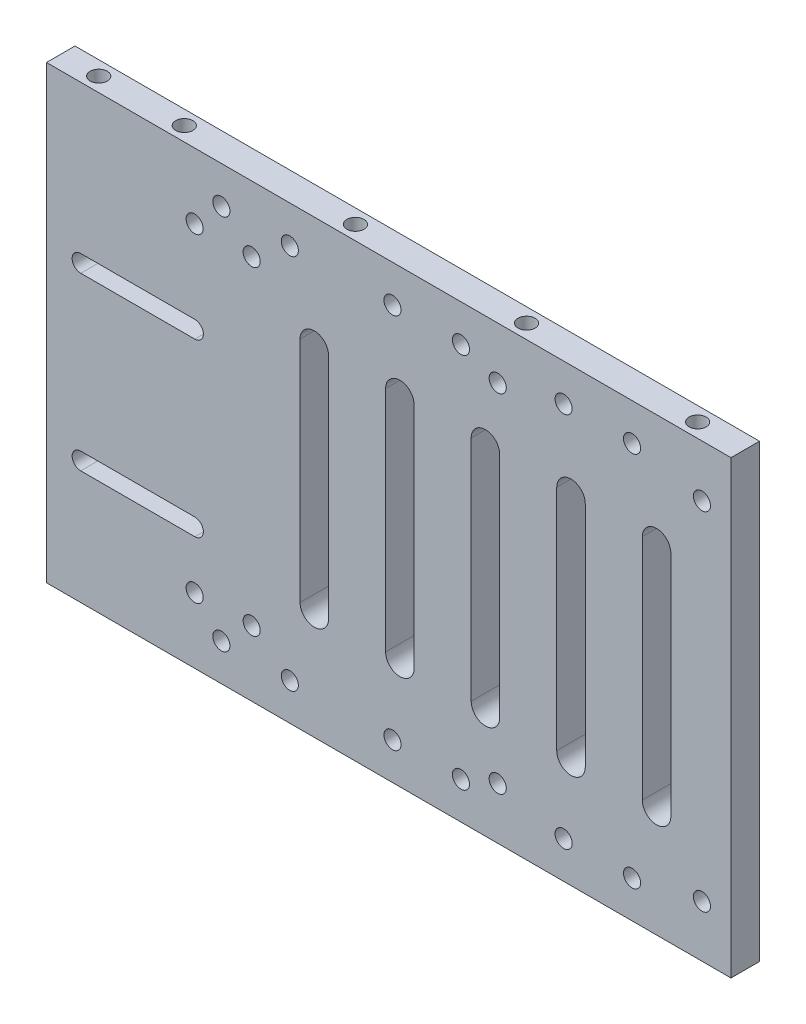
SolidWorks part; units mm, degrees
ref_plane "前视基准面" through (0, 0, 0) normal (0, 0, 1) x (1, 0, 0)
ref_plane "上视基准面" through (0, 0, 0) normal (0, 1, 0) x (1, 0, 0)
ref_plane "右视基准面" through (0, 0, 0) normal (1, 0, 0) x (0, 0, -1)
other "Configuration Table"
sketch "草图1" plane through (0, 0, 0) normal (0, 0, 1) x (1, 0, 0)
  line L1 (-60, -39.5) -> (60, -39.5)
  line L2 (-60, -39.5) -> (-60, 39.5)
  line L3 (-60, 39.5) -> (60, 39.5)
  line L4 (60, -39.5) -> (60, 39.5)
  line L5 (-60, -39.5) -> (60, 39.5) construction
  line L6 (-60, 39.5) -> (60, -39.5) construction
  point P0 (0, 0)
  dimension "D1" = 79
  dimension "D2" = 120
extrude "凸台-拉伸1" add sketch "草图1" along normal blind 5
sketch "草图2" plane through (0, 0, 0) normal (0, 0, -1) x (-1, 0, 0)
  circle A0 centre (-42.656, -33) radius 3.1
  circle A1 centre (-30.656, -33) radius 3.1
extrude "切除-拉伸1" cut sketch "草图2" against normal blind 1.5
sketch "草图3" plane through (0, 0, 1.5) normal (0, 0, -1) x (-1, 0, 0)
  circle A0 centre (-42.656, -33) radius 1.5
  circle A1 centre (-30.656, -33) radius 1.5
extrude "切除-拉伸2" cut sketch "草图3" against normal through all
pattern_linear "阵列(线性)1" count 3 spacing 30 along (-1, 0, 0) of "切除-拉伸1", "切除-拉伸2"
mirror "镜向2" about plane through (0, 0, 0) normal (0, 1, 0) of "阵列(线性)1"
sketch "草图4" plane through (0, 0, 0) normal (0, 0, -1) x (-1, 0, 0)
  line L0 (34, 12) -> (54, 12) construction
  line L1 (34, 15.1) -> (54, 15.1)
  line L2 (34, 8.9) -> (54, 8.9)
  line L3 (60, 39.5) -> (60, -39.5) construction
  line L4 (34.3421, -3) -> (54.815, -3) construction
  line L5 (34.3421, 17) -> (34.3421, -23) construction
  line L6 (54.815, 17) -> (54.815, -6) construction
  line L7 (34, -18) -> (54, -18) construction
  line L8 (34, -21.1) -> (54, -21.1)
  line L9 (34, -14.9) -> (54, -14.9)
  arc A4 (34, 15.1) -> (34, 8.9) centre (34, 12) ccw
  arc A5 (54, 8.9) -> (54, 15.1) centre (54, 12) ccw
  arc A6 (34, -21.1) -> (34, -14.9) centre (34, -18) cw
  arc A7 (54, -14.9) -> (54, -21.1) centre (54, -18) cw
  point P8 (44, 12)
  point P17 (44, -18)
  dimension "D1" = 20
  dimension "D2" = 6
extrude "切除-拉伸3" cut sketch "草图4" against normal blind 1.5
sketch "草图5" plane through (0, 0, 1.5) normal (0, 0, -1) x (-1, 0, 0)
  line L0 (54, 12) -> (34, 12) construction
  line L1 (54, 10.5) -> (34, 10.5)
  line L2 (54, 13.5) -> (34, 13.5)
  line L3 (60, 39.5) -> (60, -39.5) construction
  line L4 (34.3421, -3) -> (54.815, -3) construction
  line L5 (54.815, 17) -> (54.815, -6) construction
  line L6 (54, -18) -> (34, -18) construction
  line L7 (54, -16.5) -> (34, -16.5)
  line L8 (54, -19.5) -> (34, -19.5)
  arc A0 (54, 10.5) -> (54, 13.5) centre (54, 12) ccw
  arc A1 (34, 13.5) -> (34, 10.5) centre (34, 12) ccw
  arc A2 (54, -16.5) -> (54, -19.5) centre (54, -18) cw
  arc A3 (34, -19.5) -> (34, -16.5) centre (34, -18) cw
  point P4 (44, 12)
  point P18 (44, -18)
  dimension "D1" = 20
  dimension "D2" = 6
extrude "切除-拉伸4" cut sketch "草图5" against normal through all
sketch "草图7" plane through (0, -39.5, 0) normal (0, -1, 0) x (1, 0, 0)
  line L0 (46.656, 31) -> (46.656, 5) construction
  circle A0 centre (51.656, 2.5) radius 1.5
  circle A1 centre (21.656, 2.5) radius 1.5
  circle A2 centre (-8.344, 2.5) radius 1.5
  circle A3 centre (-38.344, 2.5) radius 1.5
  circle A4 centre (-53.344, 2.5) radius 1.5
  dimension "D1" = 5
  dimension "D2" = 15
extrude "切除-拉伸6" cut sketch "草图7" against normal blind 5
mirror "镜向3" about plane through (0, 0, 0) normal (0, 1, 0) of "切除-拉伸6"
sketch "草图9" plane through (0, 0, 0) normal (0, 0, -1) x (-1, 0, 0)
  line L0 (-46.9526, -20.2662) -> (-46.9526, 19.7338) construction
  line L1 (-49.4526, -20.2662) -> (-49.4526, 19.7338)
  line L2 (-44.4526, -20.2662) -> (-44.4526, 19.7338)
  line L3 (-31.9526, -20.2662) -> (-31.9526, 19.7338) construction
  line L4 (-34.4526, -20.2662) -> (-34.4526, 19.7338)
  line L5 (-29.4526, -20.2662) -> (-29.4526, 19.7338)
  line L6 (-16.9526, -20.2662) -> (-16.9526, 19.7338) construction
  line L7 (-19.4526, -20.2662) -> (-19.4526, 19.7338)
  line L8 (-14.4526, -20.2662) -> (-14.4526, 19.7338)
  line L9 (-1.9526, -20.2662) -> (-1.9526, 19.7338) construction
  line L10 (-4.4526, -20.2662) -> (-4.4526, 19.7338)
  line L11 (0.5474, -20.2662) -> (0.5474, 19.7338)
  line L12 (13.0474, -20.2662) -> (13.0474, 19.7338) construction
  line L13 (10.5474, -20.2662) -> (10.5474, 19.7338)
  line L14 (15.5474, -20.2662) -> (15.5474, 19.7338)
  circle A0 centre (24.0277, -28) radius 1.5 construction
  circle A1 centre (34.0277, -28) radius 1.5 construction
  circle A2 centre (24.0277, 28) radius 1.5 construction
  circle A3 centre (34.0277, 28) radius 1.5 construction
  circle A4 centre (24.0277, -28) radius 1.5
  circle A5 centre (34.0277, -28) radius 1.5
  circle A6 centre (24.0277, 28) radius 1.5
  circle A7 centre (34.0277, 28) radius 1.5
  arc A8 (-49.4526, -20.2662) -> (-44.4526, -20.2662) centre (-46.9526, -20.2662) ccw
  arc A9 (-44.4526, 19.7338) -> (-49.4526, 19.7338) centre (-46.9526, 19.7338) ccw
  arc A10 (-34.4526, -20.2662) -> (-29.4526, -20.2662) centre (-31.9526, -20.2662) ccw
  arc A11 (-29.4526, 19.7338) -> (-34.4526, 19.7338) centre (-31.9526, 19.7338) ccw
  circle A16 centre (-19.1038, 30.4) radius 1.5
  circle A17 centre (-54.9038, 30.4) radius 1.5
  circle A18 centre (-19.1038, -30.4) radius 1.5
  circle A19 centre (-54.9038, -30.4) radius 1.5
  arc A20 (-19.4526, -20.2662) -> (-14.4526, -20.2662) centre (-16.9526, -20.2662) ccw
  arc A21 (-14.4526, 19.7338) -> (-19.4526, 19.7338) centre (-16.9526, 19.7338) ccw
  arc A22 (-4.4526, -20.2662) -> (0.5474, -20.2662) centre (-1.9526, -20.2662) ccw
  arc A23 (0.5474, 19.7338) -> (-4.4526, 19.7338) centre (-1.9526, 19.7338) ccw
  arc A24 (10.5474, -20.2662) -> (15.5474, -20.2662) centre (13.0474, -20.2662) ccw
  arc A25 (15.5474, 19.7338) -> (10.5474, 19.7338) centre (13.0474, 19.7338) ccw
  point P17 (-46.9526, -0.2662)
  point P31 (-31.9526, -0.2662)
  point P38 (-16.9526, -0.2662)
  point P45 (-1.9526, -0.2662)
  point P52 (13.0474, -0.2662)
  dimension "D1" = 5
extrude "切除-拉伸7" cut sketch "草图9" against normal through all
